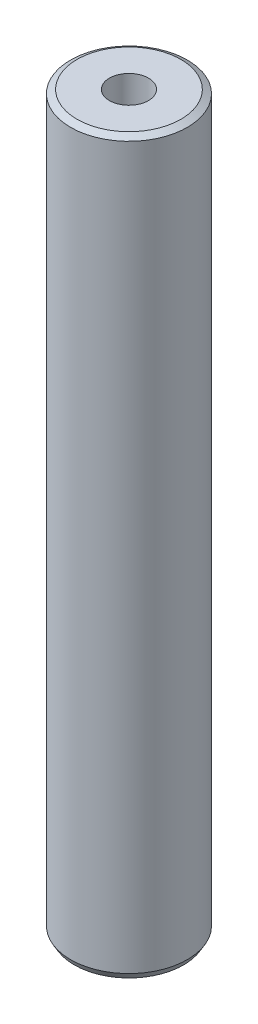
SolidWorks part; units mm, degrees
ref_plane "Front Plane" through (0, 0, 0) normal (0, 0, 1) x (1, 0, 0)
ref_plane "Top Plane" through (0, 0, 0) normal (0, 1, 0) x (1, 0, 0)
ref_plane "Right Plane" through (0, 0, 0) normal (1, 0, 0) x (0, 0, -1)
sketch "Sketch1" plane through (0, 0, 0) normal (0, 1, 0) x (1, 0, 0)
  circle A0 centre (0, 0) radius 17.5
  dimension "SHAFT_OD" = 35
extrude "Boss-Extrude1" add sketch "Sketch1" along normal blind 219.1231
sketch "Sketch2" plane through (0, 0, 0) normal (0, 1, 0) x (1, 0, 0)
  circle A0 centre (0, 0) radius 5.8514
  dimension "BORE_D" = 11.7029
extrude "Cut-Extrude1" cut sketch "Sketch2" along normal through all
chamfer "Chamfer1" distance 1.1204 angle 60 2 edges at (0, 219.1231, 17.5) (0, 0, 17.5) first distance on face at (0, 219.1231, 17.5) first distance on face at (0, 0, 5.8514)
